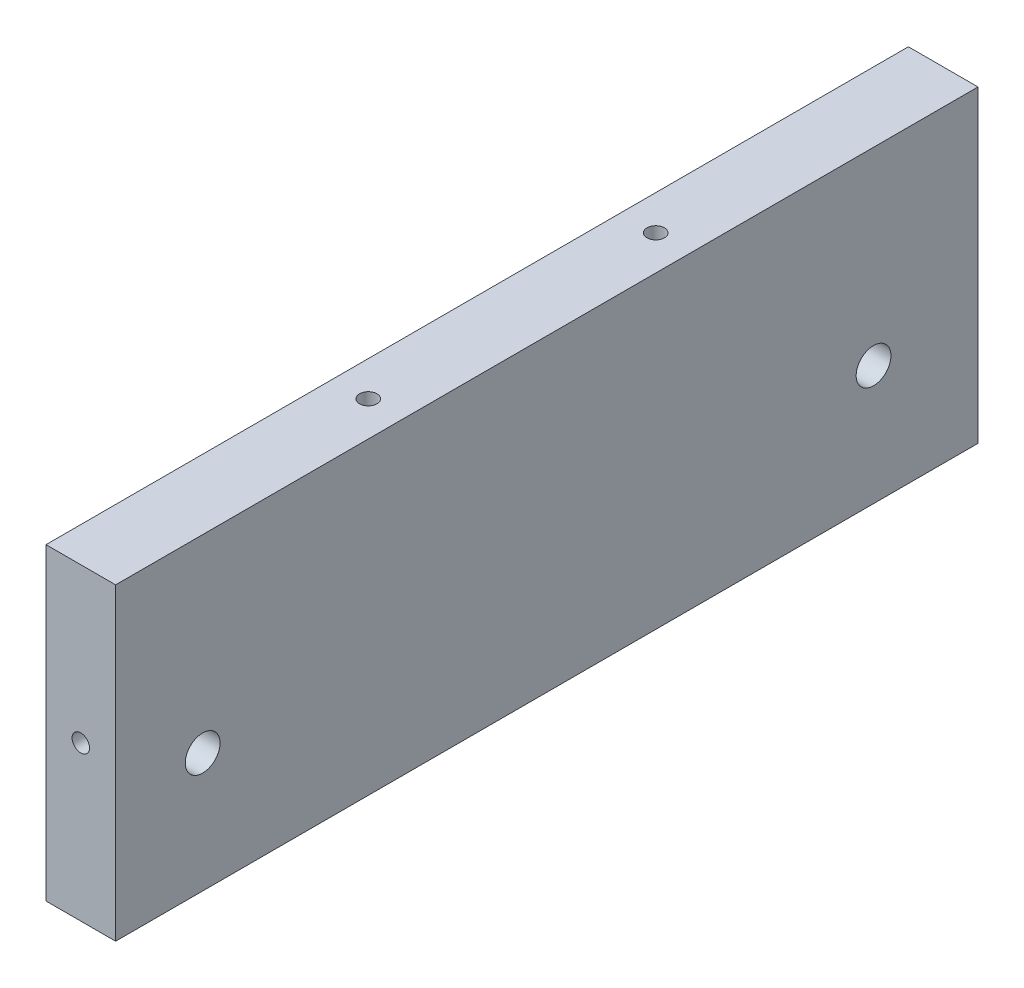
SolidWorks part; units mm, degrees
material "Beech"
ref_plane "Front Plane" through (0, 0, 0) normal (0, 0, 1) x (1, 0, 0)
ref_plane "Top Plane" through (0, 0, 0) normal (0, 1, 0) x (1, 0, 0)
ref_plane "Right Plane" through (0, 0, 0) normal (1, 0, 0) x (0, 0, -1)
sketch "Sketch1" plane through (0, 0, 0) normal (0, 0, 1) x (1, 0, 0)
  line L0 (-16.7045, 12.7) -> (-231.3045, 12.7) construction
  line L1 (-244.0045, 69) -> (-231.3045, 69)
  line L2 (-244.0045, 69) -> (-244.0045, 12.7)
  line L3 (-244.0045, 12.7) -> (-231.3045, 12.7)
  line L4 (-231.3045, 69) -> (-231.3045, 12.7)
  dimension "D1" = 12.7
extrude "Boss-Extrude1" add sketch "Sketch1" along normal up to surface (157.3 mm away)
hole_wizard "Hole1" positions "Sketch2" profile "Sketch3" legacy
sketch "Sketch2" plane through (-124.0045, 0, 91.1757) normal (0, -1, 0) x (1, 0, 0)
  line L1 (0, 465.9538) -> (0, 66.1243) construction
  line L2 (126.073, 146.2179) -> (113.373, 146.2179) construction
  line L6 (119.723, 195.4304) -> (119.723, 97.0054) construction
  line L10 (68.923, 196.0654) -> (68.923, 111.2929) construction
  point P1 (113.65, 39.9076)
  point P3 (113.65, -64.959)
  point P5 (-94.6, 72.4743)
  point P7 (94.6, 72.4743)
  point P9 (0, 72.4743)
  point P11 (0, 104.2243)
  point P13 (0, 351.6538)
  point P15 (0, 213.0704)
  point P17 (40.9792, 213.0704)
  point P19 (166.7958, 213.0704)
  point P21 (207.775, 351.6538)
  point P23 (207.775, 244.1214)
  point P25 (207.775, 136.589)
  point P27 (207.775, 48.5243)
  point P29 (207.775, -78.4757)
  point P33 (-207.775, -78.4757)
  point P34 (-207.775, 48.5243)
  point P35 (-207.775, 136.589)
  point P36 (-207.775, 244.1214)
  point P37 (-207.775, 351.6538)
  point P38 (-166.7958, 213.0704)
  point P39 (-40.9792, 213.0704)
  point P40 (-113.65, -64.959)
  point P41 (-113.65, 39.9076)
  point P58 (119.723, 146.2179)
  point P65 (119.723, 109.7054)
  point P68 (119.723, 182.7304)
  point P78 (18.123, 109.7054)
  point P79 (18.123, 182.7304)
  point P81 (0, 0)
  point P82 (113.65, 23.941)
  point P83 (0, 0)
  point P84 (207.775, -78.2752)
  point P85 (209.3058, -90.1558)
  point P86 (207.775, -78.4757)
  point P88 (113.65, -64.959)
  point P90 (207.775, 48.5243)
  point P92 (0, 0)
  point P93 (207.775, 136.589)
  point P95 (207.775, 244.1214)
  point P97 (207.775, 351.6538)
  point P99 (113.65, 39.9076)
  point P101 (94.6, 72.4743)
  point P103 (0, 72.4743)
  point P105 (0, 104.2243)
  point P107 (0, 0)
  point P108 (0, 213.0704)
  point P110 (0, 0)
  point P111 (0, 351.6538)
  point P113 (-40.9792, 213.0704)
  point P115 (-94.6, 72.4743)
  point P117 (-166.7958, 213.0704)
  point P119 (-113.65, -64.959)
  point P121 (0, 66.1243)
  dimension "D1" = 12.7
  dimension "D2" = 12.7
sketch "Sketch3" plane through (-10.3545, 0, 131.0833) normal (1, 0, 0) x (0, 0, -1)
  line L0 (0, 0) -> (0, 32.7039)
  line L1 (0, 32.7039) -> (1.5875, 31.75)
  line L2 (1.5875, 31.75) -> (1.5875, 4.0177)
  line L3 (1.5875, 4.0177) -> (5.08, 0)
  line L4 (5.08, 0) -> (0, 0)
  line L5 (0, -14.3089) -> (0, 102.4216) construction
  line L6 (0, 32.7039) -> (-1.5875, 31.75) construction
  line L7 (-1.5875, 4.0177) -> (-5.08, 0) construction
  dimension "Diameter" = 3.175
  dimension "Depth" = 31.75
  dimension "C-Sink Diameter" = 10.16
  dimension "C-Sink Angle" = 82
  dimension "Drill Angle" = 118
hole_wizard "Hole2" positions "Sketch4" profile "Sketch5" legacy
sketch "Sketch4" plane through (-124.0045, 0, 66.1243) normal (0, -1, 0) x (-1, 0, 0)
  line L1 (0, 465.9538) -> (0, 66.1243) construction
  line L2 (126.073, 146.2179) -> (113.373, 146.2179) construction
  line L6 (119.723, 195.4304) -> (119.723, 97.0054) construction
  line L10 (68.923, 196.0654) -> (68.923, 111.2929) construction
  point P1 (113.65, 39.9076)
  point P3 (113.65, -64.959)
  point P5 (-94.6, 72.4743)
  point P7 (94.6, 72.4743)
  point P9 (0, 72.4743)
  point P11 (0, 104.2243)
  point P13 (0, 351.6538)
  point P15 (0, 213.0704)
  point P17 (40.9792, 213.0704)
  point P19 (166.7958, 213.0704)
  point P21 (207.775, 351.6538)
  point P23 (207.775, 244.1214)
  point P25 (207.775, 136.589)
  point P27 (207.775, 48.5243)
  point P29 (207.775, -78.4757)
  point P33 (-207.775, -78.4757)
  point P34 (-207.775, 48.5243)
  point P35 (-207.775, 136.589)
  point P36 (-207.775, 244.1214)
  point P37 (-207.775, 351.6538)
  point P38 (-166.7958, 213.0704)
  point P39 (-40.9792, 213.0704)
  point P40 (-113.65, -64.959)
  point P41 (-113.65, 39.9076)
  point P58 (119.723, 146.2179)
  point P65 (119.723, 109.7054)
  point P68 (119.723, 182.7304)
  point P78 (18.123, 109.7054)
  point P79 (18.123, 182.7304)
  point P81 (0, 0)
  point P82 (113.65, 23.941)
  point P83 (0, 0)
  point P84 (207.775, -78.2752)
  point P85 (209.3058, -90.1558)
  point P86 (207.775, -78.4757)
  point P88 (113.65, -64.959)
  point P90 (207.775, 48.5243)
  point P92 (0, 0)
  point P93 (207.775, 136.589)
  point P95 (207.775, 244.1214)
  point P97 (207.775, 351.6538)
  point P99 (113.65, 39.9076)
  point P101 (94.6, 72.4743)
  point P103 (0, 72.4743)
  point P105 (0, 104.2243)
  point P107 (0, 0)
  point P108 (0, 213.0704)
  point P110 (0, 0)
  point P111 (0, 351.6538)
  point P113 (-40.9792, 213.0704)
  point P115 (-94.6, 72.4743)
  point P117 (-166.7958, 213.0704)
  point P119 (-113.65, -64.959)
  point P121 (0, 66.1243)
  dimension "D1" = 12.7
  dimension "D2" = 12.7
sketch "Sketch5" plane through (-237.6545, 0, 26.2167) normal (1, 0, 0) x (0, 0, -1)
  line L0 (0, 0) -> (0, 32.7039)
  line L1 (0, 32.7039) -> (1.5875, 31.75)
  line L2 (1.5875, 31.75) -> (1.5875, 4.0177)
  line L3 (1.5875, 4.0177) -> (5.08, 0)
  line L4 (5.08, 0) -> (0, 0)
  line L5 (0, -14.3089) -> (0, 102.4216) construction
  line L6 (0, 32.7039) -> (-1.5875, 31.75) construction
  line L7 (-1.5875, 4.0177) -> (-5.08, 0) construction
  dimension "Diameter" = 3.175
  dimension "Depth" = 31.75
  dimension "C-Sink Diameter" = 10.16
  dimension "C-Sink Angle" = 82
  dimension "Drill Angle" = 118
hole_wizard "Hole" positions "Sketch6" profile "Sketch7" legacy
sketch "Sketch6" plane through (-124.0045, 277.2867, 170) normal (0, 0, 1) x (-1, 0, 0)
  point P0 (113.65, 236.4367)
  point P2 (207.775, 236.4367)
sketch "Sketch7" plane through (-237.6545, 40.85, 170) normal (1, 0, 0) x (0, -1, 0)
  line L0 (0, 0) -> (0, 32.7039)
  line L1 (0, 32.7039) -> (1.5875, 31.75)
  line L2 (1.5875, 31.75) -> (1.5875, 4.0177)
  line L3 (1.5875, 4.0177) -> (5.08, 0)
  line L4 (5.08, 0) -> (0, 0)
  line L5 (0, -14.3089) -> (0, 102.4216) construction
  line L6 (0, 32.7039) -> (-1.5875, 31.75) construction
  line L7 (-1.5875, 4.0177) -> (-5.08, 0) construction
  dimension "Diameter" = 3.175
  dimension "Depth" = 31.75
  dimension "C-Sink Diameter" = 10.16
  dimension "C-Sink Angle" = 82
  dimension "Drill Angle" = 118
hole_wizard "Hole3" positions "Sketch8" profile "Sketch9" legacy
sketch "Sketch8" plane through (-124.0045, 88.05, 66.1243) normal (0, 1, 0) x (1, 0, 0)
  point P15 (-162.3, -97.5257)
  point P34 (-113.65, -38.7424)
  point P36 (-113.65, 13.691)
  point P54 (162.3, -97.5257)
  point P55 (113.65, -38.7424)
  point P56 (113.65, 13.691)
  point P71 (63.85, 72.4743)
  point P73 (0, 72.4743)
  point P74 (-63.85, 72.4743)
sketch "Sketch9" plane through (-286.3045, 88.05, 163.65) normal (1, 0, 0) x (0, 0, 1)
  line L0 (0, 0) -> (0, 32.7039)
  line L1 (0, 32.7039) -> (1.5875, 31.75)
  line L2 (1.5875, 31.75) -> (1.5875, 4.0177)
  line L3 (1.5875, 4.0177) -> (5.08, 0)
  line L4 (5.08, 0) -> (0, 0)
  line L5 (0, -14.3089) -> (0, 102.4216) construction
  line L6 (0, 32.7039) -> (-1.5875, 31.75) construction
  line L7 (-1.5875, 4.0177) -> (-5.08, 0) construction
  dimension "Diameter" = 3.175
  dimension "Depth" = 31.75
  dimension "C-Sink Diameter" = 10.16
  dimension "C-Sink Angle" = 82
  dimension "Drill Angle" = 118
hole_wizard "Hole4" positions "Sketch10" profile "Sketch11" legacy
sketch "Sketch10" plane through (-124.0045, 88.05, 91.1757) normal (0, 1, 0) x (-1, 0, 0)
  point P15 (-162.3, -97.5257)
  point P34 (-113.65, -38.7424)
  point P36 (-113.65, 13.691)
  point P54 (162.3, -97.5257)
  point P55 (113.65, -38.7424)
  point P56 (113.65, 13.691)
  point P71 (63.85, 72.4743)
  point P73 (0, 72.4743)
  point P74 (-63.85, 72.4743)
sketch "Sketch11" plane through (38.2955, 88.05, -6.35) normal (1, 0, 0) x (0, 0, 1)
  line L0 (0, 0) -> (0, 32.7039)
  line L1 (0, 32.7039) -> (1.5875, 31.75)
  line L2 (1.5875, 31.75) -> (1.5875, 4.0177)
  line L3 (1.5875, 4.0177) -> (5.08, 0)
  line L4 (5.08, 0) -> (0, 0)
  line L5 (0, -14.3089) -> (0, 102.4216) construction
  line L6 (0, 32.7039) -> (-1.5875, 31.75) construction
  line L7 (-1.5875, 4.0177) -> (-5.08, 0) construction
  dimension "Diameter" = 3.175
  dimension "Depth" = 31.75
  dimension "C-Sink Diameter" = 10.16
  dimension "C-Sink Angle" = 82
  dimension "Drill Angle" = 118
hole_wizard "1/4 (0.25) Diameter Hole1" positions "Sketch12" profile "Sketch13" hole size "1/4" standard "ANSI Inch" end condition through all
sketch "Sketch12" plane through (-244.0045, 0, 0) normal (-1, 0, 0) x (0, 0, 1)
  point P0 (141.425, 34.5)
  point P2 (19.05, 34.5)
sketch "Sketch13" plane through (-244.0045, 34.5, 141.425) normal (0, 1, 0) x (0, 0, 1)
  line L0 (0, 0) -> (0, 12.7)
  line L1 (0, 12.7) -> (3.175, 12.7)
  line L2 (3.175, 12.7) -> (3.175, 0)
  line L5 (3.175, 0) -> (0, 0)
  line L11 (0, -6.35) -> (0, 107.95) construction
  dimension "Thru Hole Dia." = 6.35
  dimension "Thru Hole Depth" = 12.7
